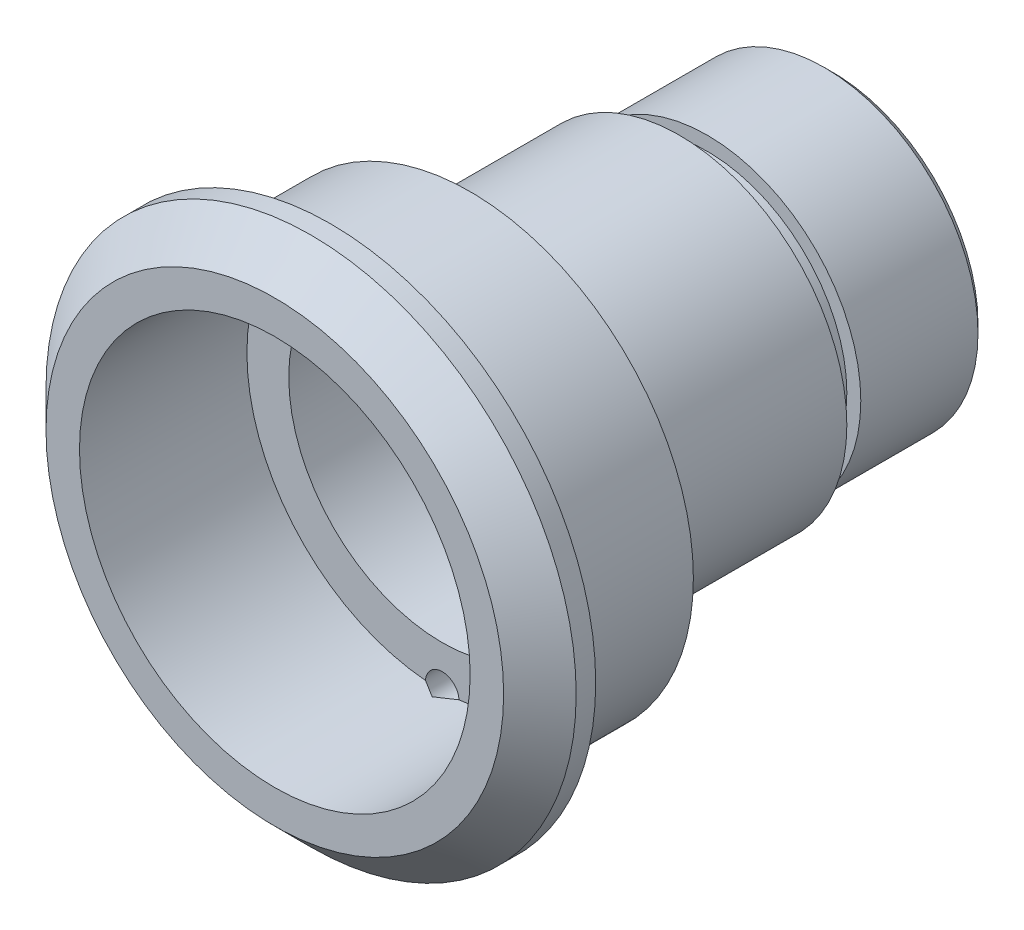
SolidWorks part; units mm, degrees
ref_plane "Front Plane" through (0, 0, 0) normal (0, 0, 1) x (1, 0, 0)
ref_plane "Top Plane" through (0, 0, 0) normal (0, 1, 0) x (1, 0, 0)
ref_plane "Right Plane" through (0, 0, 0) normal (1, 0, 0) x (0, 0, -1)
sketch "Sketch1" plane through (0, 0, 0) normal (0, 0, 1) x (1, 0, 0)
  circle A0 centre (0, 0) radius 9.5
  dimension "D1" = 19
extrude "Boss-Extrude1" add sketch "Sketch1" against normal blind 20
sketch "Sketch2" plane through (0, 0, -20) normal (0, 0, -1) x (-1, 0, 0)
  circle A0 centre (0, 0) radius 8
  dimension "D1" = 16
extrude "Cut-Extrude1" cut sketch "Sketch2" against normal offset from surface (18 mm away) 2 flip side to cut up to face at (9.5, 0, 0)
sketch "Sketch3" plane through (0, 0, -20) normal (0, 0, -1) x (-1, 0, 0)
  circle A0 centre (0, 0) radius 6
  dimension "D1" = 12
extrude "Cut-Extrude2" cut sketch "Sketch3" against normal offset from surface (13 mm away) 5 flip side to cut up to face at (9.5, 0, -2)
sketch "Sketch4" plane through (0, 0, -20) normal (0, 0, -1) x (-1, 0, 0)
  circle A0 centre (0, 0) radius 5.5
  dimension "D1" = 11
extrude "Cut-Extrude3" cut sketch "Sketch4" against normal offset from surface (5.5 mm away) 7.5 flip side to cut up to face at (8, 0, -7)
sketch "Sketch5" plane through (0, 0, 0) normal (1, 0, 0) x (0, 0, -1)
  line L0 (0, 0) -> (20, 0) construction
  line L1 (0, 9.5) -> (0, -9.5) construction
  line L2 (20, -5.5) -> (20, 5.5) construction
  line L4 (14.5, 5.5) -> (15.5, 5.5)
  line L5 (14.5, 5.5) -> (14.5, 5)
  line L6 (14.5, 5) -> (15.5, 5)
  line L7 (15.5, 5.5) -> (15.5, 5)
  dimension "D1" = 10
  dimension "D2" = 1
revolve "Cut-Revolve1" cut sketch "Sketch5" angle 360 about L0
chamfer "Chamfer1" distance 0.3 angle 45 1 edges at (-5.5, 0, -20)
chamfer "Chamfer2" distance 1.3 angle 45 1 edges at (9.5, 0, 0)
sketch "Sketch6" plane through (0, 0, 0) normal (1, 0, 0) x (0, 0, -1)
  line L0 (0, 0) -> (20, 0) construction
  line L1 (20, -5.2) -> (20, 5.2) construction
  line L2 (7.2, -7.033) -> (6.7768, -6.3)
  line L3 (7, -8) -> (7, 8) construction
  line L4 (7, -6) -> (14.5, -6) construction
  line L5 (6.95, -6) -> (7.2, -6)
  line L6 (7, -6.433) -> (7, -6) construction
  line L7 (7.2, -7.033) -> (7.2, -6)
  line L8 (7.2, -6.433) -> (7.2, -6) construction
  arc A0 (6.7768, -6.3) -> (6.95, -6) centre (6.95, -6.2) cw
  dimension "D3" = 0.2
  dimension "D1" = 60
  dimension "D2" = 0.2
  dimension "D4" = 0.25
revolve "Cut-Revolve2" cut sketch "Sketch6" angle 360 about L0
sketch "Sketch7" plane through (0, 0, 0) normal (0, 0, 1) x (1, 0, 0)
  circle A0 centre (0, 0) radius 4.05
  dimension "D1" = 8.1
extrude "Cut-Extrude4" cut sketch "Sketch7" against normal through all
sketch "Sketch8" plane through (0, 0, -20) normal (0, 0, -1) x (-1, 0, 0)
  circle A0 centre (0, 0) radius 4.5
  dimension "D1" = 9
extrude "Cut-Extrude5" cut sketch "Sketch8" against normal blind 4.5
sketch "Sketch9" plane through (0, 0, -15.5) normal (0, 0, -1) x (-1, 0, 0)
  circle A0 centre (0, 0) radius 4.45
  dimension "D1" = 8.9
extrude "Cut-Extrude9" cut sketch "Sketch9" against normal offset from surface (0.2 mm away) 8.3 up to face at (6.6866, 0, -7)
sketch "Sketch10" plane through (0, 0, 0) normal (0, 0, 1) x (1, 0, 0)
  circle A0 centre (0, 0) radius 7
  dimension "D1" = 14
extrude "Cut-Extrude11" cut sketch "Sketch10" against normal offset from surface (6 mm away) 1 up to face at (6.6866, 0, -7)
sketch "Sketch11" plane through (0, 0, -6) normal (0, 0, 1) x (1, 0, 0)
  circle A0 centre (0, 0) radius 5.5
  dimension "D1" = 11
extrude "Cut-Extrude12" cut sketch "Sketch11" against normal offset from surface (5.6 mm away) 4.6 up to face at (6.6866, 0, -7) offset beyond the face yes
sketch "Sketch12" plane through (0, 0, -11.6) normal (0, 0, 1) x (1, 0, 0)
  circle A0 centre (0, 0) radius 5.25
  dimension "D1" = 10.5
extrude "Cut-Extrude13" cut sketch "Sketch12" against normal offset from surface (1.9 mm away) 6.5 up to face at (6.6866, 0, -7) offset beyond the face yes
chamfer "Chamfer3" distance 1.2 angle 45 1 edges at (4.05, 0, -13.5)
hole_wizard "Ø1.2 (1.2) Diameter Hole1" positions "Sketch16" profile "Sketch15" hole size "Ø1.2" standard "DIN"
sketch "Sketch16" plane through (0, 0, -7) normal (0, 0, -1) x (-1, 0, 0)
  circle A0 centre (0, 0) radius 7 construction
  point P0 (0, -7)
  point P2 (0, 7)
  dimension "D1" = 14
sketch "Sketch15" plane through (0, -7, -7) normal (1, 0, 0) x (0, 1, 0)
  line L0 (0, 0) -> (0, 1.3605)
  line L1 (0, 1.3605) -> (0.6, 1)
  line L2 (0.6, 1) -> (0.6, 0)
  line L5 (0.6, 0) -> (0, 0)
  line L10 (0, 1.3605) -> (-0.6, 1) construction
  line L11 (0, -6.35) -> (0, 107.95) construction
  dimension "Hole Dia." = 1.2
  dimension "Hole Depth" = 1
  dimension "Drill Angle" = 118
